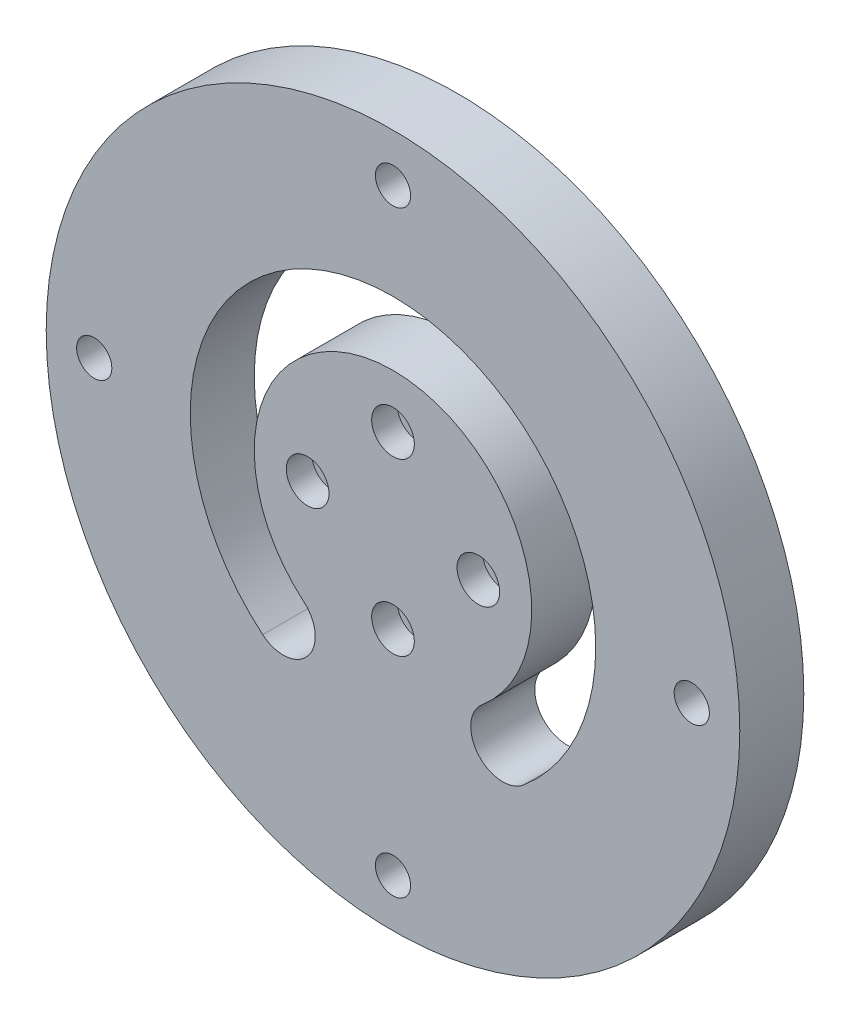
SolidWorks part; units mm, degrees
ref_plane "Front Plane" through (0, 0, 0) normal (0, 0, 1) x (1, 0, 0)
ref_plane "Top Plane" through (0, 0, 0) normal (0, 1, 0) x (1, 0, 0)
ref_plane "Right Plane" through (0, 0, 0) normal (1, 0, 0) x (0, 0, -1)
sketch "Sketch1" plane through (0, 0, 0) normal (0, 0, 1) x (1, 0, 0)
  circle A0 centre (0, 0) radius 32.5
  dimension "D1" = 65
extrude "Boss-Extrude1" add sketch "Sketch1" along normal blind 6
sketch "Sketch16" plane through (0, 0, 6) normal (0, 0, 1) x (1, 0, 0)
  line L0 (-8, 0) -> (8, 0) construction
  line L1 (0, 0) -> (0, -8) construction
  line L2 (0, 0) -> (0, 8) construction
  circle A0 centre (8, 0) radius 1.1
  circle A1 centre (-8, 0) radius 1.1
  circle A2 centre (0, -8) radius 1.1
  circle A3 centre (0, 8) radius 1.1
  point P6 (0, 0)
  dimension "D1" = 2.2
  dimension "D2" = 8
  dimension "D3" = 16
  dimension "D4" = 8
extrude "Cut-Extrude8" cut sketch "Sketch16" against normal through all
sketch "Sketch17" plane through (0, 0, 6) normal (0, 0, 1) x (1, 0, 0)
  circle A0 centre (8, 0) radius 2
  circle A1 centre (-8, 0) radius 2
  circle A2 centre (0, -8) radius 2
  circle A3 centre (0, 8) radius 2
  dimension "D1" = 4
extrude "Cut-Extrude9" cut sketch "Sketch17" against normal blind 2.4
sketch "Sketch12" plane through (0, 0, 6) normal (0, 0, 1) x (1, 0, 0)
  line L0 (0, 0) -> (0, 28) construction
  circle A4 centre (0, 28) radius 1.65
  circle A5 centre (28, 0) radius 1.65
  circle A6 centre (0, -28) radius 1.65
  circle A7 centre (-28, 0) radius 1.65
  point P3 (-12.6376, -27.4281)
  point P4 (0, 0)
  point P14 (0, 0)
  dimension "D3" = 4
  dimension "D1" = 3.3
  dimension "D2" = 28
extrude "Cut-Extrude10" cut sketch "Sketch12" against normal through all
sketch "Sketch18" plane through (0, 0, 0) normal (0, 0, -1) x (-1, 0, 0)
  line L1 (1.6166, 30.8) -> (-1.6166, 30.8)
  line L2 (-1.6166, 30.8) -> (-3.2332, 28)
  line L3 (-3.2332, 28) -> (-1.6166, 25.2)
  line L4 (-1.6166, 25.2) -> (1.6166, 25.2)
  line L5 (1.6166, 25.2) -> (3.2332, 28)
  line L6 (3.2332, 28) -> (1.6166, 30.8)
  line L7 (29.6166, 2.8) -> (26.3834, 2.8)
  line L8 (26.3834, 2.8) -> (24.7668, 0)
  line L9 (24.7668, 0) -> (26.3834, -2.8)
  line L10 (26.3834, -2.8) -> (29.6166, -2.8)
  line L11 (29.6166, -2.8) -> (31.2332, 0)
  line L12 (31.2332, 0) -> (29.6166, 2.8)
  line L13 (1.6166, -25.2) -> (-1.6166, -25.2)
  line L14 (-1.6166, -25.2) -> (-3.2332, -28)
  line L15 (-3.2332, -28) -> (-1.6166, -30.8)
  line L16 (-1.6166, -30.8) -> (1.6166, -30.8)
  line L17 (1.6166, -30.8) -> (3.2332, -28)
  line L18 (3.2332, -28) -> (1.6166, -25.2)
  line L19 (-26.3834, 2.8) -> (-29.6166, 2.8)
  line L20 (-29.6166, 2.8) -> (-31.2332, 0)
  line L21 (-31.2332, 0) -> (-29.6166, -2.8)
  line L22 (-29.6166, -2.8) -> (-26.3834, -2.8)
  line L23 (-26.3834, -2.8) -> (-24.7668, 0)
  line L24 (-24.7668, 0) -> (-26.3834, 2.8)
  circle A0 centre (0, 28) radius 2.8 construction
  circle A1 centre (28, 0) radius 2.8 construction
  circle A2 centre (0, -28) radius 2.8 construction
  circle A3 centre (-28, 0) radius 2.8 construction
  dimension "D1" = 5.6
extrude "Cut-Extrude11" cut sketch "Sketch18" against normal blind 3
sketch "Sketch19" plane through (0, 0, 6) normal (0, 0, 1) x (1, 0, 0)
  line L0 (0, 0) -> (0, -19.652) construction
  line L1 (0, 0) -> (12.213, -14.5548) construction
  line L2 (0, 0) -> (-12.213, -14.5548) construction
  arc A0 (12.213, -14.5548) -> (-12.213, -14.5548) centre (0, 0) ccw
  arc A1 (8.3562, -9.9586) -> (-8.3562, -9.9586) centre (0, 0) ccw
  arc A2 (-12.213, -14.5548) -> (-8.3562, -9.9586) centre (-10.2846, -12.2567) ccw
  arc A3 (8.3562, -9.9586) -> (12.213, -14.5548) centre (10.2846, -12.2567) ccw
  dimension "D1" = 6
  dimension "D3" = 13
  dimension "D2" = 40
extrude "Cut-Extrude12" cut sketch "Sketch19" against normal through all
